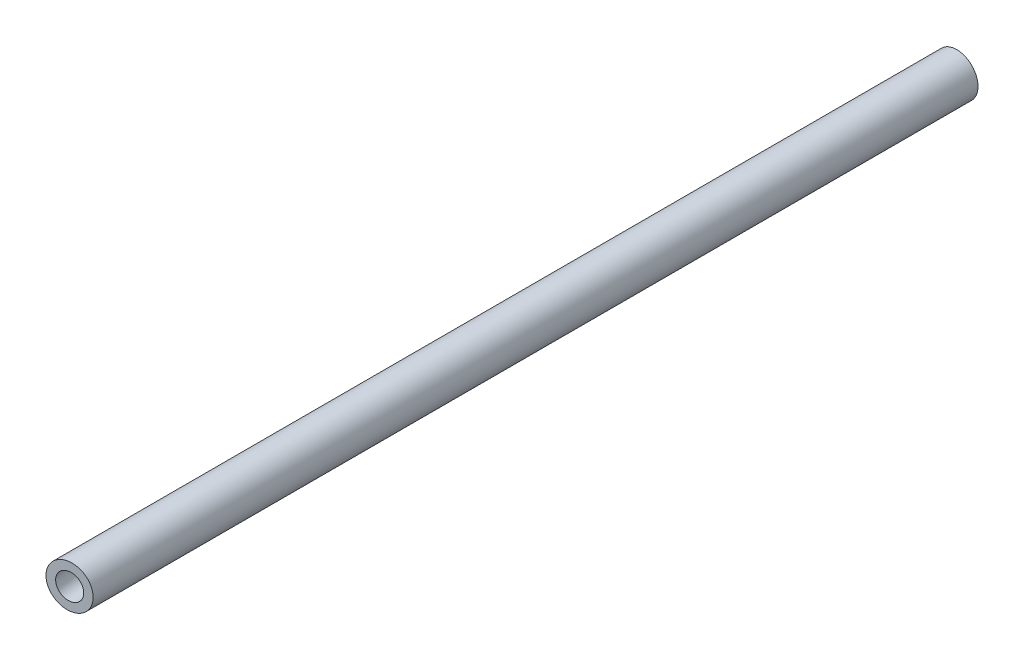
SolidWorks part; units mm, degrees
ref_plane "Płaszczyzna przednia" through (0, 0, 0) normal (0, 0, 1) x (1, 0, 0)
ref_plane "Płaszczyzna górna" through (0, 0, 0) normal (0, 1, 0) x (1, 0, 0)
ref_plane "Płaszczyzna prawa" through (0, 0, 0) normal (1, 0, 0) x (0, 0, -1)
sketch "Szkic1" plane through (0, 0, 0) normal (0, 0, 1) x (1, 0, 0)
  circle A0 centre (0, 0) radius 10
extrude "Dodanie-wyciągnięcie1" add sketch "Szkic1" along normal blind 500
sketch "Szkic2" plane through (0, 0, 0) normal (0, 0, -1) x (-1, 0, 0)
  circle A0 centre (0, 0) radius 6
extrude "Wytnij-wyciągnięcie1" cut sketch "Szkic2" against normal blind 118
sketch "Szkic3" plane through (0, 0, 0) normal (0, 1, 0) x (1, 0, 0)
  line L0 (-10, -500) -> (10, -500)
  line L1 (10, -500) -> (15.0546, -497.3667)
  line L3 (-10, -500) -> (15.0546, -497.3667)
  dimension "D1" = 6
extrude "Wytnij-wyciągnięcie2" cut sketch "Szkic3" against normal blind 35 and the other way blind 35
sketch "Szkic4" plane through (51.8687, 0, 493.4973) normal (0.1045, 0, 0.9945) x (0.9945, 0, -0.1045)
  circle A0 centre (-52.0994, 0) radius 6
extrude "Wytnij-wyciągnięcie3" cut sketch "Szkic4" against normal blind 35
sketch "Szkic5" plane through (0, 0, 0) normal (0, 1, 0) x (1, 0, 0)
  line L0 (10, -497.8979) -> (10, 0) construction
  line L1 (-10, 0) -> (10, 0)
  line L2 (-10, 0) -> (-10, -83)
  line L3 (-10, -83) -> (10, -83)
  line L4 (10, 0) -> (10, -83)
  dimension "D1" = 83
extrude "Wytnij-wyciągnięcie4" cut sketch "Szkic5" against normal blind 20 and the other way blind 20
